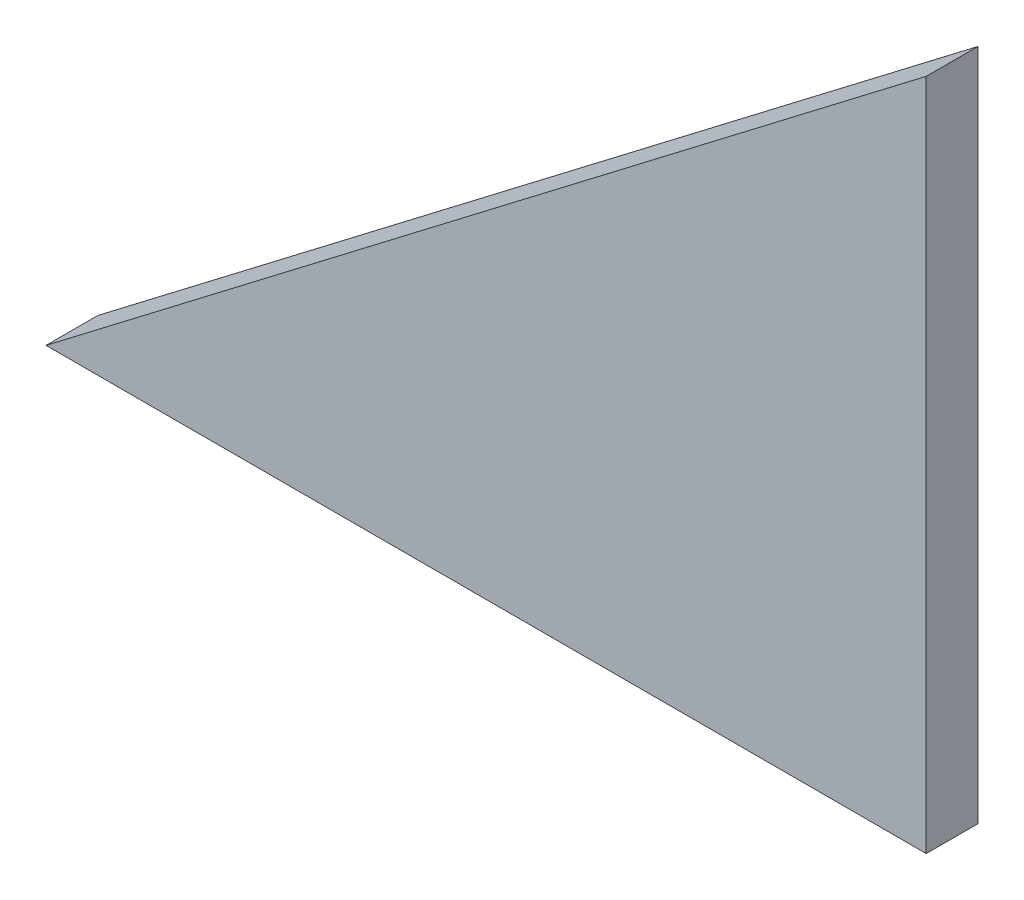
SolidWorks part; units mm, degrees
ref_plane "Ön Düzlem" through (0, 0, 0) normal (0, 0, 1) x (1, 0, 0)
ref_plane "Üst Düzlem" through (0, 0, 0) normal (0, 1, 0) x (1, 0, 0)
ref_plane "Sağ Düzlem" through (0, 0, 0) normal (1, 0, 0) x (0, 0, -1)
sketch "Çizim1" plane through (0, 0, 0) normal (0, 0, 1) x (1, 0, 0)
  line L0 (0, 0) -> (170, 0)
  line L1 (170, 0) -> (170, 130)
  line L2 (170, 130) -> (0, 0)
  dimension "D1" = 170
  dimension "D2" = 130
  dimension "D3" = 214.0093
base flange "Taban-Flanş1" sketch "Çizim1" thickness 10 reverse thickness direction no parameters "D1"=5
sketch "Büküm-Çizgileri1" [suppressed] plane through (0, 0, 0) normal (0, 1, 0) x (1, 0, 0)
sketch "Sınırlandırma-Kutusu1" [suppressed] plane through (0, 0, 0) normal (0, 1, 0) x (1, 0, 0)
sheet metal parameters "Sac-Levha1" thickness 10 parameters "D1"=5
flat pattern "Düz-Çoğaltma1" [suppressed]
sketch "Büküm-Çizgileri2" plane through (0, 0, 0) normal (0, 1, 0) x (1, 0, 0)
sketch3d "Sınırlandırma-Kutusu2" [suppressed]
  line L0 (0, 0, 0) -> (170, 0, 0) construction
  line L1 (0, 130, 0) -> (170, 130, 0) construction
  line L2 (0, 0, 0) -> (0, 130, 0) construction
  line L3 (170, 0, 0) -> (170, 130, 0) construction
